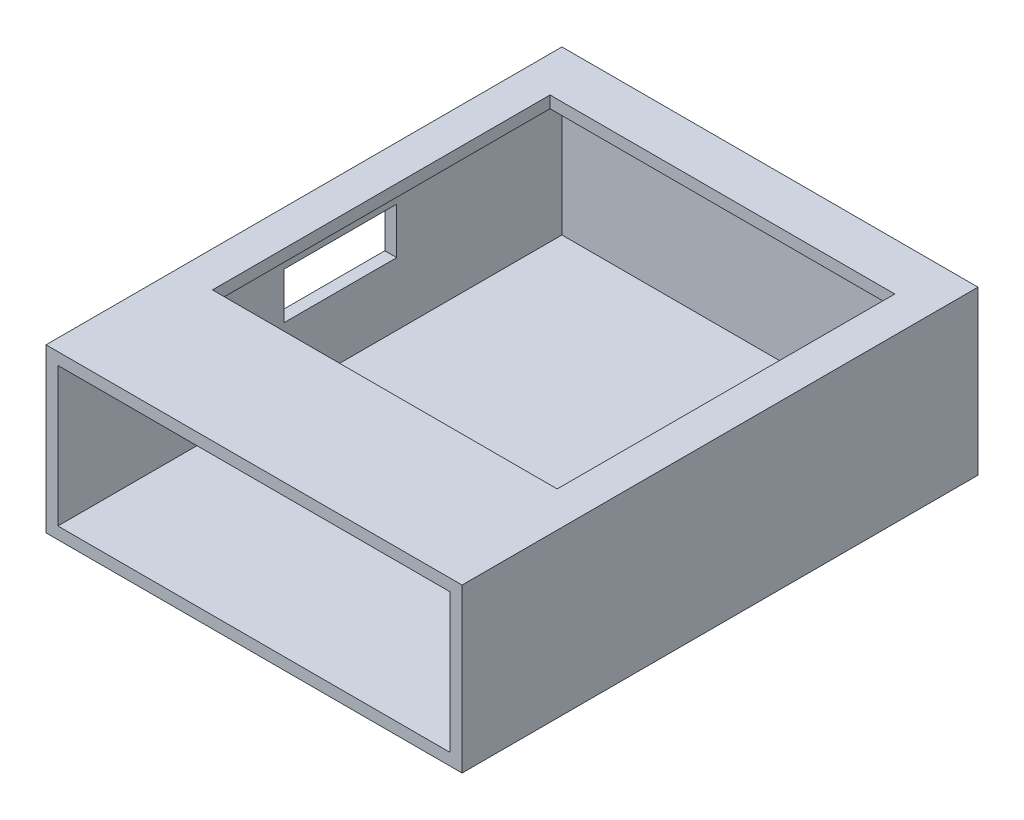
SolidWorks part; units mm, degrees
ref_plane "前视基准面" through (0, 0, 0) normal (0, 0, 1) x (1, 0, 0)
ref_plane "上视基准面" through (0, 0, 0) normal (0, 1, 0) x (1, 0, 0)
ref_plane "右视基准面" through (0, 0, 0) normal (1, 0, 0) x (0, 0, -1)
other "Configuration Table"
sketch "草图1" plane through (0, 0, 0) normal (0, 1, 0) x (1, 0, 0)
  line L0 (0, 0) -> (33, 0)
  line L1 (33, 0) -> (33, 42.4)
  line L2 (33, 42.4) -> (0, 42.4)
  line L3 (0, 42.4) -> (0, 0)
extrude "凸台-拉伸1" add sketch "草图1" along normal blind 11.7
shell "抽壳1" thickness 1 removed face at (16.5, 11.7, -21.2) removed face at (16.5, 5.85, 0) outward yes
sketch "草图2" plane through (-1, 0, 0) normal (-1, 0, 0) x (0, 0, 1)
  line L0 (-28.5, 9.2) -> (-19, 9.2)
  line L1 (-19, 9.2) -> (-19, 5.3)
  line L2 (-19, 5.3) -> (-28.5, 5.3)
  line L3 (-28.5, 5.3) -> (-28.5, 9.2)
  line L10 (-11.25, 8.3) -> (-9.65, 8.3)
  line L11 (-9.65, 8.3) -> (-9.65, 6.1)
  line L12 (-9.65, 6.1) -> (-12.85, 6.1)
  line L13 (-12.85, 6.1) -> (-12.85, 8.3)
  line L14 (-12.85, 8.3) -> (-11.25, 8.3)
  point P5 (-11.25, 8.3)
  point P19 (-23.75, 9.2)
extrude "切除-左侧接口" cut sketch "草图2" against normal up to next contours L14 L10 L11 L12 L13 | L3 L0 L1 L2
sketch "草图4" plane through (0, 11.7, 0) normal (0, 1, 0) x (1, 0, 0)
  line L0 (-1, 0) -> (34, 0)
  line L1 (34, 0) -> (34, 3)
  line L2 (34, 0) -> (34, 43.4) construction
  line L3 (31, 11) -> (2, 11)
  line L4 (-1, 43.4) -> (-1, 0) construction
  line L5 (-1, 3) -> (-1, 0)
  line L6 (-1, 43.4) -> (-1, 0)
  line L7 (34, 0) -> (34, 43.4)
  line L8 (34, 43.4) -> (-1, 43.4)
  line L9 (-1, 43.4) -> (-1, 40.4)
  line L10 (2, 39.4) -> (31, 39.4)
  line L11 (-1, 43.4) -> (-1, 0)
  line L12 (34, 0) -> (-1, 0)
  line L13 (2, 39.4) -> (2, 11)
  line L14 (31, 39.4) -> (31, 11)
  line L15 (34, 0) -> (34, 43.4)
  point P11 (0, 0)
  point P19 (0, 0)
extrude "凸台-拉伸2" add sketch "草图4" along normal blind 1 contours L8 L6 L0 L7 | L3 L13 L10 L14
